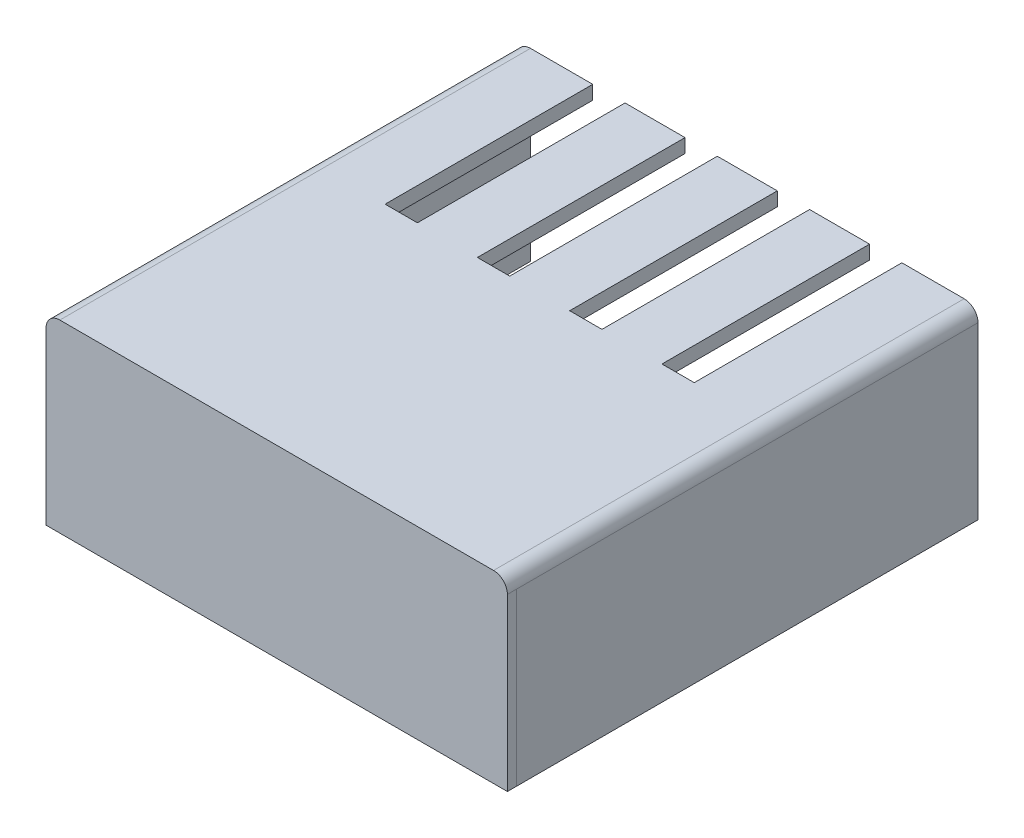
SolidWorks part; units mm, degrees
ref_plane "Alzado" through (0, 0, 0) normal (0, 0, 1) x (1, 0, 0)
ref_plane "Planta" through (0, 0, 0) normal (0, 1, 0) x (1, 0, 0)
ref_plane "Vista lateral" through (0, 0, 0) normal (1, 0, 0) x (0, 0, -1)
sketch "Croquis1" plane through (0, 0, 0) normal (0, 1, 0) x (1, 0, 0)
  line L1 (-50, 70) -> (50, 70)
  line L2 (-50, 70) -> (-50, -32)
  line L3 (-50, -32) -> (50, -32)
  line L4 (50, 70) -> (50, -32)
  point P5 (0, -32)
  point P6 (0, 70)
  dimension "D1" = 32
  dimension "D2" = 100
  dimension "D3" = 70
extrude "Saliente-Extruir1" add sketch "Croquis1" along normal blind 3
sketch "Croquis2" plane through (0, 0, 0) normal (0, -1, 0) x (1, 0, 0)
  line L0 (-50, -70) -> (-50, 32) construction
  line L1 (-50, -14.5) -> (-47, -14.5)
  line L2 (-50, -14.5) -> (-50, -29.5)
  line L3 (-50, -29.5) -> (-47, -29.5)
  line L4 (-47, -14.5) -> (-47, -29.5)
  point P6 (-47, -22)
  point P8 (-48.5, -14.5)
  dimension "D1" = 15
  dimension "D2" = 3
  dimension "D3" = 22
extrude "Saliente-Extruir2" add sketch "Croquis2" along normal blind 50
sketch "Croquis3" plane through (0, 0, 0) normal (0, -1, 0) x (1, 0, 0)
  line L0 (50, -70) -> (-50, -70) construction
  line L1 (-47, -14.5) -> (-50, -14.5)
  line L2 (-47, -14.5) -> (-47, 32)
  line L3 (-47, 32) -> (-50, 32)
  line L4 (-50, -14.5) -> (-50, 32)
  line L5 (-50, -29.5) -> (-47, -29.5)
  line L6 (-50, -29.5) -> (-50, -70)
  line L7 (-50, -70) -> (-47, -70)
  line L8 (-47, -29.5) -> (-47, -70)
extrude "Saliente-Extruir3" add sketch "Croquis3" along normal blind 37
sketch "Croquis4" plane through (0, 0, 32) normal (0, 0, 1) x (1, 0, 0)
  line L0 (-47, -37) -> (-47, 0) construction
  line L1 (-47, 0) -> (50, 0)
  line L2 (-47, 0) -> (-47, -37)
  line L3 (-47, -37) -> (50, -37)
  line L4 (50, 0) -> (50, -37)
extrude "Saliente-Extruir4" add sketch "Croquis4" against normal blind 2
sketch "Croquis5" plane through (50, 0, 0) normal (1, 0, 0) x (0, 0, -1)
  line L0 (-30, 0) -> (70, 0) construction
  line L1 (-30, 0) -> (70, 0)
  line L2 (-30, 0) -> (-30, -37)
  line L3 (-30, -37) -> (70, -37)
  line L4 (70, 0) -> (70, -37)
extrude "Saliente-Extruir5" add sketch "Croquis5" against normal blind 3 separate body
fillet "Redondeo2" radius 3 2 edges at (50, 3, -19) (-50, 3, -19)
fillet "Redondeo3" radius 3 1 edges at (-47, -43.5, -29.5)
sketch "Croquis6" plane through (0, 3, 0) normal (0, 1, 0) x (1, 0, 0)
  line L0 (47, 70) -> (-47, 70) construction
  point P0 (-37.3169, 70)
  point P1 (-21.942, 70)
  point P4 (-1.3397, 70)
  point P5 (29.8713, 70)
sketch "Croquis7" plane through (0, 0, -70) normal (0, 0, -1) x (-1, 0, 0)
  line L0 (-50, 0) -> (47, 0) construction
  line L1 (47, 0) -> (47, -37) construction
  line L2 (-47, 3) -> (47, 3) construction
  line L3 (33.5, -3) -> (26.5, -3)
  line L4 (33.5, -3) -> (33.5, 3)
  line L5 (33.5, 3) -> (26.5, 3)
  line L6 (26.5, -3) -> (26.5, 3)
  line L7 (33.5, -3) -> (26.5, 3) construction
  line L8 (33.5, 3) -> (26.5, -3) construction
  line L9 (13.5, -3) -> (13.5, 3)
  line L10 (13.5, -3) -> (6.5, -3)
  line L11 (6.5, -3) -> (6.5, 3)
  line L12 (13.5, 3) -> (6.5, 3)
  line L13 (-6.5, -3) -> (-6.5, 3)
  line L14 (-6.5, -3) -> (-13.5, -3)
  line L15 (-13.5, -3) -> (-13.5, 3)
  line L16 (-6.5, 3) -> (-13.5, 3)
  line L17 (-26.5, -3) -> (-26.5, 3)
  line L18 (-26.5, -3) -> (-33.5, -3)
  line L19 (-33.5, -3) -> (-33.5, 3)
  line L20 (-26.5, 3) -> (-33.5, 3)
  point P0 (30, 0)
  point P5 (30, 0)
  point P13 (10, -3)
  dimension "D1" = 17
  dimension "D2" = 7
  dimension "D4" = 20
  dimension "D3" = 4
extrude "Cortar-Extruir1" cut sketch "Croquis7" against normal blind 45
